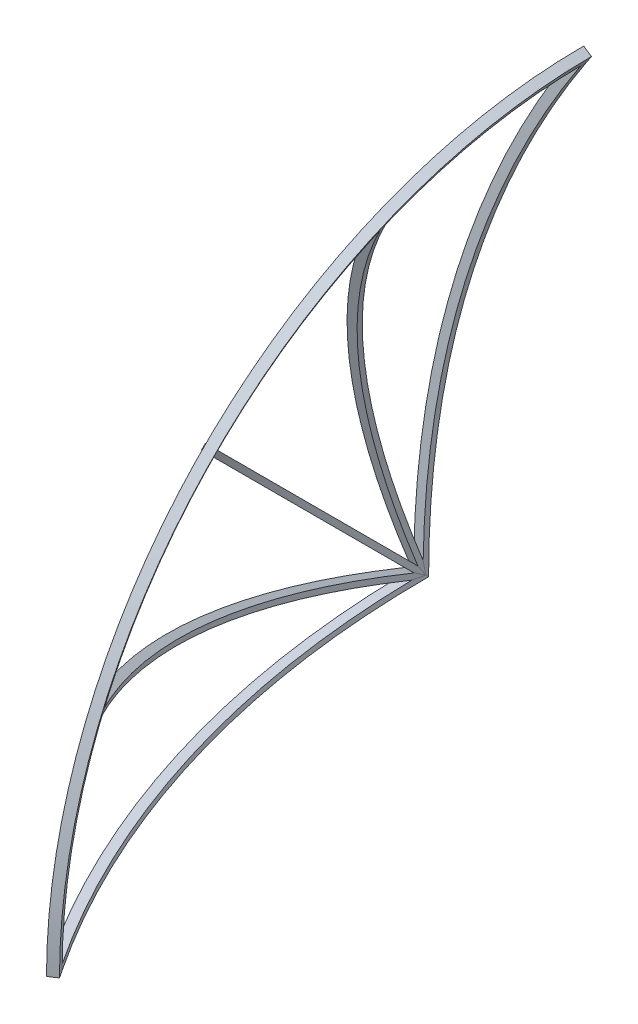
SolidWorks part; units mm, degrees
ref_plane "Front Plane" through (0, 0, 0) normal (0, 0, 1) x (1, 0, 0)
ref_plane "Top Plane" through (0, 0, 0) normal (0, 1, 0) x (1, 0, 0)
ref_plane "Right Plane" through (0, 0, 0) normal (1, 0, 0) x (0, 0, -1)
sketch "Sketch2" plane through (0, 0, 0) normal (0, 0, 1) x (1, 0, 0)
  line L0 (0, 0) -> (340, 0) construction
  line L1 (340, 0) -> (340, 1130) construction
  line L2 (0, 0) -> (2047.79, 0) construction
  line L3 (0, 0) -> (20, 0) construction
  line L4 (0, 0) -> (20, 0)
  line L5 (2047.79, 0) -> (2067.79, 0) construction
  line L6 (340, 1129.9988) -> (356.6793, 1118.9625)
  arc A0 (0, 0) -> (340, 1129.9988) centre (2047.79, 0) cw
  arc A1 (20, 0) -> (356.6793, 1118.9625) centre (2047.79, 0) cw
  dimension "D1" = 20
extrude "Boss-Extrude1" add sketch "Sketch2" along normal blind 12 contours A0 L6 A1 L4
ref_plane "Plane4" through (0, 6, 0) normal (0, 1, 0) x (1, 0, 0)
ref_plane "Plane5" through (0, 0, 6) normal (0, 0, 1) x (1, 0, 0)
ref_axis "Axis1" through (-103.3895, 6, 6) along (1, 0, 0)
pattern_circular "CirPattern1" count 5 every 22.5 about axis through (-103.3895, 6, 6) along (1, 0, 0) of "Boss-Extrude1"
sketch "Sketch3" plane through (0, 0, 0) normal (1, 0, 0) x (0, 0, -1)
  line L0 (0, 0) -> (0, 11.2742)
  line L1 (0, 0) -> (0, 1118.9625) construction
  line L2 (0, 11.2742) -> (5.7486, 11.2742)
  line L3 (5.7486, 11.2742) -> (5.7486, -8.4382)
  line L4 (5.7486, -8.4382) -> (-12.083, -8.4382)
  line L5 (-12.083, -8.4382) -> (-12, 0)
  line L6 (-12, 0) -> (0, 0)
extrude "Cut-Extrude1" cut sketch "Sketch3" along normal through all
sketch "Sketch4" plane through (0, 0, 0) normal (0, 0, -1) x (-1, 0, 0)
  line L0 (-340, 1129.9988) -> (-356.6793, 1118.9625)
  line L1 (-356.6793, 1118.9625) -> (-367.7156, 1135.6418)
  line L2 (-367.7156, 1135.6418) -> (-351.0363, 1146.6781)
  line L3 (-351.0363, 1146.6781) -> (-340, 1129.9988)
  line L4 (-367.7156, 1135.6418) -> (-367.7156, 1183.9946) construction
  dimension "D1" = 20
  dimension "D2" = 56.508
sketch "Sketch5" plane through (0, 0, 0) normal (1, 0, 0) x (0, 0, -1)
  arc A0 (0, 1130) -> (-1130, 0) centre (0, 0) ccw
sweep "Sweep1" add profiles "Sketch4" path "Sketch5"
